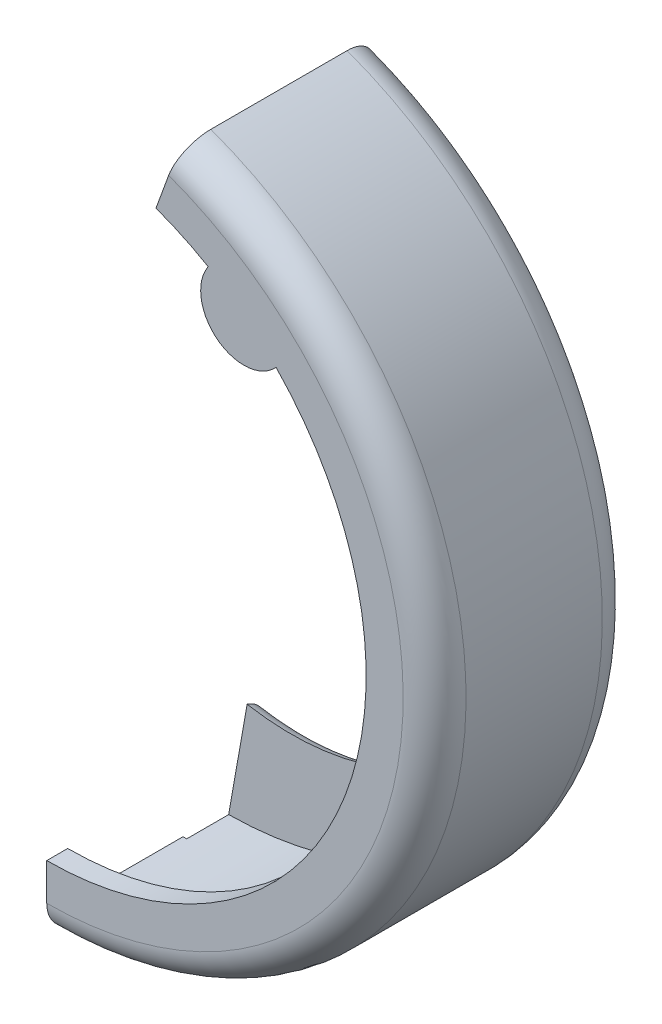
SolidWorks part; units mm, degrees
ref_plane "Front Plane" through (0, 0, 0) normal (0, 0, 1) x (1, 0, 0)
ref_plane "Top Plane" through (0, 0, 0) normal (0, 1, 0) x (1, 0, 0)
ref_plane "Right Plane" through (0, 0, 0) normal (1, 0, 0) x (0, 0, -1)
sketch "Sketch1" plane through (0, 0, 0) normal (1, 0, 0) x (0, 0, -1)
  line L1 (-25, -10) -> (-10, -10)
  line L2 (-25, -10) -> (-25, 25)
  line L3 (-25, 25) -> (-10, 25)
  line L4 (-10, -10) -> (-10, 25)
revolve "Revolve1" add sketch "Sketch1" angle 160 about L3 reverse direction yes
shell "Shell1" thickness 2 removed face at (5.9854, 41.4446, 17.5) removed face at (0, 7.5, 17.5) outward yes
sketch "Sketch5" plane through (0, 0, 27) normal (0, 0, 1) x (1, 0, 0)
  line L0 (0, 25) -> (12.6547, 59.7686) construction
  line L1 (0, 25) -> (0, -12) construction
  arc A0 (10.422, 53.6342) -> (0, -5.4719) centre (0, 25) cw
  point P8 (0, 0)
extrude "Cut-Extrude4" cut sketch "Sketch5" against normal blind 6 and the other way through all flip side to cut contours A0
sketch "Sketch7" plane through (0, 0, 8) normal (0, 0, -1) x (-1, 0, 0)
  line L0 (-12.6547, 59.7686) -> (0, -12)
extrude "Cut-Extrude5" cut sketch "Sketch7" against normal blind 6 and the other way through all contours L0
sketch "Sketch9" plane through (0, 0, 27) normal (0, 0, 1) x (1, 0, 0)
  circle A0 centre (18.8095, 48.9737) radius 4.1241
  arc A1 (0, -5.4719) -> (10.422, 53.6342) centre (0, 25) ccw construction
extrude "Boss-Extrude1" add sketch "Sketch9" against normal up to vertex (2 mm away) contours A0 up to point (10.422, 53.6342, 25)
fillet "Fillet4" radius 3 1 edges at (36.4379, 18.575, 27)
fillet "Fillet5" radius 3 1 edges at (36.4379, 18.575, 8)
sketch "Sketch13" plane through (0, 0, 8) normal (0, 0, -1) x (-1, 0, 0)
  line L0 (-0.5297, -8.9959) -> (-12.125, 56.7645) construction
  arc A0 (-2.1159, 0) -> (-10.5388, 47.7686) centre (-6.3274, 23.8843) cw
extrude "Cut-Extrude15" cut sketch "Sketch13" against normal blind 2 and the other way through all flip side to cut contours A0
fillet "Fillet9" radius 3 1 edges at (30.2117, 19.6729, 8)
